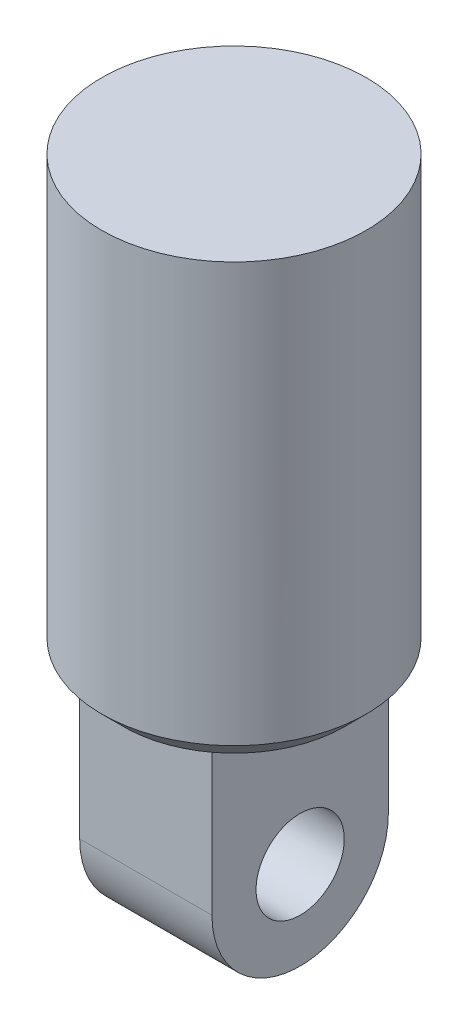
SolidWorks part; units mm, degrees
material "AISI 1020"
ref_plane "Front Plane" through (0, 0, 0) normal (0, 0, 1) x (1, 0, 0)
ref_plane "Top Plane" through (0, 0, 0) normal (0, 1, 0) x (1, 0, 0)
ref_plane "Right Plane" through (0, 0, 0) normal (1, 0, 0) x (0, 0, -1)
sketch "Sketch1" plane through (0, 0, 0) normal (0, 0, 1) x (1, 0, 0)
  line L0 (0, 0) -> (30, 0)
  line L1 (30, 0) -> (30, -100)
  line L2 (30, -100) -> (0, -100)
  line L3 (0, -100) -> (0, 0)
  line L4 (0, 0) -> (0, 29.4048) construction
  dimension "D1" = 60
  dimension "D2" = 100
revolve "Revolve1" add sketch "Sketch1" angle 360 about L4
sketch "Sketch2" plane through (0, 0, 0) normal (1, 0, 0) x (0, 0, -1)
  line L0 (-20, -132) -> (-20, -100)
  line L1 (-30, -100) -> (30, -100) construction
  line L2 (-20, -100) -> (20, -100)
  line L3 (20, -100) -> (20, -132)
  line L4 (0, 0) -> (0, -100) construction
  line L5 (30, 0) -> (-30, 0) construction
  line L6 (0, -100) -> (0, -132) construction
  arc A0 (-20, -132) -> (20, -132) centre (0, -132) ccw
  circle A1 centre (0, -132) radius 10
  dimension "D1" = 40
  dimension "D2" = 20
  dimension "D3" = 32
extrude "Boss-Extrude1" add sketch "Sketch2" along normal mid plane 30
chamfer "Chamfer1" distance 5 angle 45 1 edges at (0, -100, -30)
equation "\"A\"= 100"
equation "\"B\"= 100"
equation "\"C\"= 100"
equation "\"D\"= 100"
equation "\"E\"= 100"
